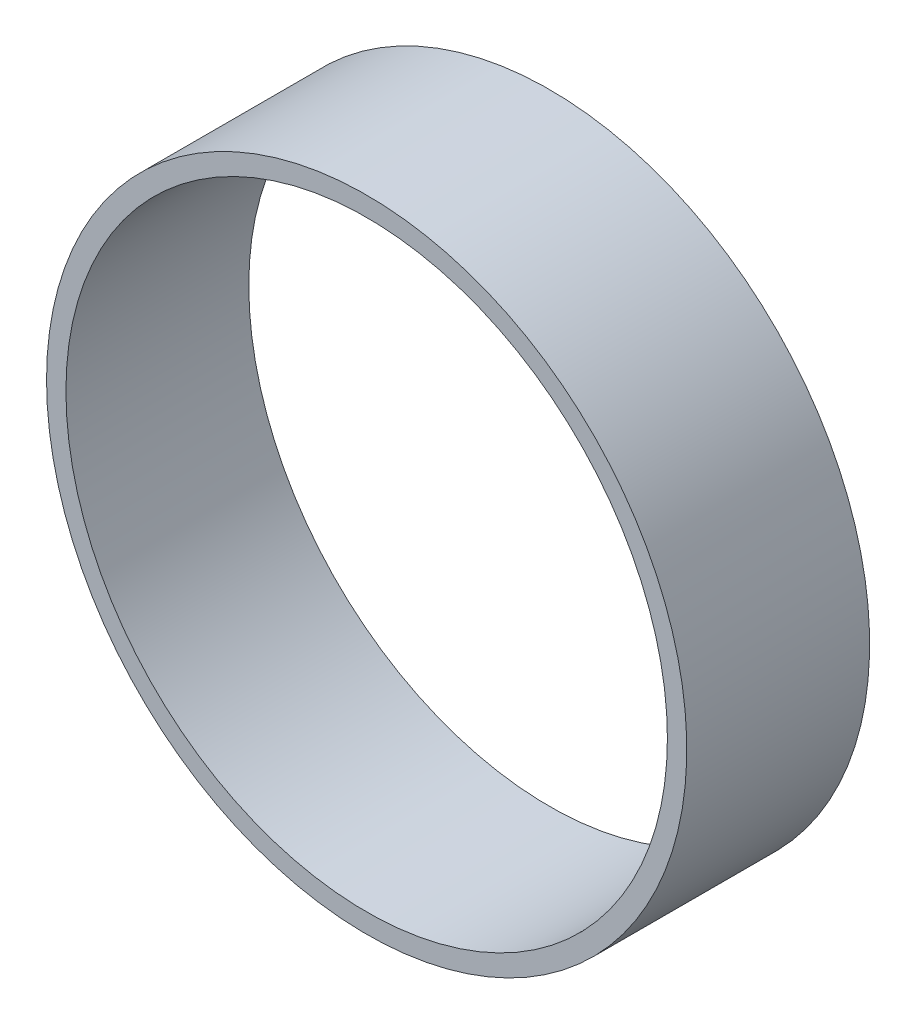
SolidWorks part; units mm, degrees
material "Plain Carbon Steel"
ref_plane "Front Plane" through (0, 0, 0) normal (0, 0, 1) x (1, 0, 0)
ref_plane "Top Plane" through (0, 0, 0) normal (0, 1, 0) x (1, 0, 0)
ref_plane "Right Plane" through (0, 0, 0) normal (1, 0, 0) x (0, 0, -1)
sketch "Sketch1" plane through (0, 0, 0) normal (1, 0, 0) x (0, 0, -1)
  line L0 (1, 82.55) -> (48.15, 82.55)
  line L1 (48.15, 82.55) -> (48.15, 77.55)
  line L2 (48.15, 77.55) -> (1, 77.55)
  line L3 (1, 77.55) -> (1, 82.55)
  dimension "D1" = 82.55
  dimension "D2" = 5
  dimension "D3" = 47.15
  dimension "D4" = 1
ref_axis "Axis1" through (0, 0, -50.5075) along (0, 0, 1)
revolve "Revolve1" add sketch "Sketch1" angle 360 about axis through (0, 0, -50.5075) along (0, 0, 1)
sketch "Sketch2" plane through (0, 0, 0) normal (1, 0, 0) x (0, 0, -1)
  line L0 (14.3098, 6.2149) -> (24.575, 0) construction
  line L1 (50.5075, 0) -> (-1.3575, 0) construction
  line L2 (24.575, 0) -> (34.8402, -6.2149) construction
  line L3 (1, 82.55) -> (1, -82.55) construction
  circle A0 centre (14.3098, 6.2149) radius 8.5
  circle A1 centre (34.8402, -6.2149) radius 8.5
  dimension "D1" = 17
  dimension "D2" = 12
  dimension "D3" = 23.575
  dimension "D4" = 31.192
extrude "Cut-Extrude1" cut sketch "Sketch2" against normal through all
pattern_circular "CirPattern1" count 20 over 360 about axis through (0, 0, -50.5075) along (0, 0, 1) of bodies 102
equation "\"TubeDiameter\"= 6.500in"
equation "\"D1@Sketch1\"=\"TubeDiameter\"/2"
